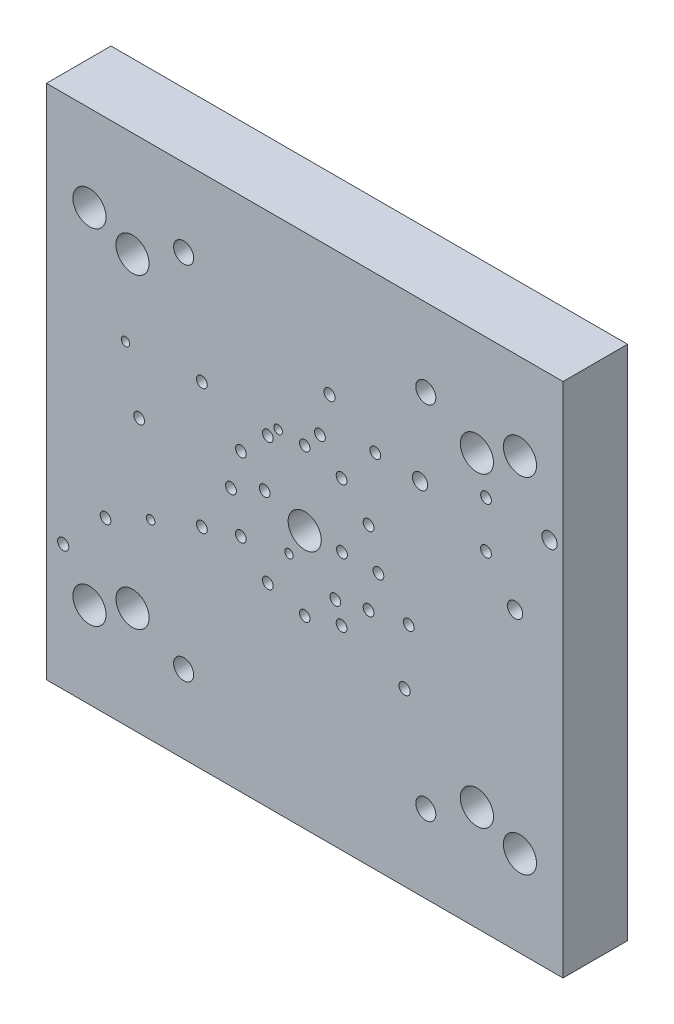
SolidWorks part; units mm, degrees
ref_plane "Front Plane" through (0, 0, 0) normal (0, 0, 1) x (1, 0, 0)
ref_plane "Top Plane" through (0, 0, 0) normal (0, 1, 0) x (1, 0, 0)
ref_plane "Right Plane" through (0, 0, 0) normal (1, 0, 0) x (0, 0, -1)
sketch "Sketch1" plane through (0, 0, 0) normal (0, 0, 1) x (1, 0, 0)
  line L1 (-152.4, 152.4) -> (152.4, 152.4)
  line L2 (-152.4, 152.4) -> (-152.4, -152.4)
  line L3 (-152.4, -152.4) -> (152.4, -152.4)
  line L4 (152.4, 152.4) -> (152.4, -152.4)
  line L5 (-152.4, 152.4) -> (152.4, -152.4) construction
  line L6 (-152.4, -152.4) -> (152.4, 152.4) construction
  point P0 (0, 0)
  dimension "D1" = 304.8
  dimension "D2" = 304.8
extrude "Boss-Extrude1" add sketch "Sketch1" along normal blind 38.1
sketch "Sketch2" plane through (0, 0, 38.1) normal (0, 0, 1) x (1, 0, 0)
  line L0 (-152.4, 0) -> (152.4, 0) construction
  line L5 (-152.4, 152.4) -> (-152.4, -152.4) construction
  line L6 (152.4, -152.4) -> (152.4, 152.4) construction
  line L7 (-152.4, -101.6) -> (152.4, -101.6) construction
  line L8 (-152.4, 101.6) -> (152.4, 101.6) construction
  line L9 (0, 101.6) -> (0, -101.6) construction
  line L10 (127, 101.6) -> (127, -101.6) construction
  line L11 (-127, 101.6) -> (-127, -101.6) construction
  circle A0 centre (-127, 101.6) radius 6.5151
  circle A1 centre (127, 101.6) radius 6.5151
  circle A2 centre (127, -101.6) radius 6.5151
  circle A3 centre (-127, -101.6) radius 6.5151
  circle A4 centre (0, 0) radius 6.5151
  dimension "D5" = 13.0302
  dimension "D1" = 101.6
  dimension "D2" = 101.6
  dimension "D3" = 127
  dimension "D4" = 127
extrude "HAAS T-Slot Holes" cut sketch "Sketch2" against normal through all
sketch "Sketch3" plane through (0, 0, 38.1) normal (0, 0, 1) x (1, 0, 0)
  circle A0 centre (-127, 101.6) radius 9.779
  circle A1 centre (127, 101.6) radius 9.779
  circle A2 centre (0, 0) radius 9.779
  circle A3 centre (127, -101.6) radius 9.779
  circle A4 centre (-127, -101.6) radius 9.779
  dimension "D1" = 19.558
extrude "HAAS Counter Bores" cut sketch "Sketch3" against normal offset from surface (22.225 mm away) 15.875 contours A0 | A1 | A2 | A3 | A4 up to face at (6.5151, 0, 0)
sketch "Sketch4" plane through (0, 0, 38.1) normal (0, 0, 1) x (1, 0, 0)
  line L0 (-127, 90.4875) -> (127, 90.4875) construction
  line L1 (-127, 30.1625) -> (127, 30.1625) construction
  line L2 (-127, 30.1625) -> (-127, -30.1625) construction
  line L3 (-127, -30.1625) -> (127, -30.1625) construction
  line L4 (127, 30.1625) -> (127, -30.1625) construction
  line L5 (-127, 30.1625) -> (127, -30.1625) construction
  line L6 (-127, -30.1625) -> (127, 30.1625) construction
  line L7 (-127, -90.4875) -> (127, -90.4875) construction
  line L8 (-101.6, 90.4875) -> (-101.6, 84.1375) construction
  line L9 (-101.6, -90.4875) -> (-101.6, -84.1375) construction
  line L10 (101.6, -90.4875) -> (101.6, -84.1375) construction
  line L11 (101.6, 90.4875) -> (101.6, 84.1375) construction
  circle A0 centre (-101.6, 90.4875) radius 6.5151
  circle A1 centre (101.6, 90.4875) radius 6.5151
  circle A2 centre (-101.6, -90.4875) radius 6.5151
  circle A3 centre (101.6, -90.4875) radius 6.5151
  point P0 (0, 0)
  dimension "D9" = 13.0302
  dimension "D1" = 60.325
  dimension "D2" = 254
  dimension "D5" = 203.2
  dimension "D6" = 25.4
  dimension "D7" = 203.2
  dimension "D8" = 6.35
  dimension "D3" = 60.325
  dimension "D4" = 60.325
extrude "Tormach T-Slot Holes" cut sketch "Sketch4" against normal through all
sketch "Sketch5" plane through (0, 0, 38.1) normal (0, 0, 1) x (1, 0, 0)
  circle A0 centre (-101.6, 90.4875) radius 9.779
  circle A1 centre (101.6, 90.4875) radius 9.779
  circle A2 centre (101.6, -90.4875) radius 9.779
  circle A3 centre (-101.6, -90.4875) radius 9.779
  dimension "D1" = 19.558
extrude "Tormach Counter bores" cut sketch "Sketch5" against normal up to surface (22.225 mm away) up to face at (-117.221, 101.6, 15.875)
sketch "Sketch6" plane through (0, 0, 38.1) normal (0, 0, 1) x (1, 0, 0)
  circle A0 centre (0, 0) radius 43.5 construction
  circle A1 centre (0, 43.5) radius 3.0734
  circle A2 centre (0, -43.5) radius 3.0734
  dimension "D1" = 87.0001
  dimension "D2" = 6.1468
extrude "Sprocket Locating Holes" cut sketch "Sketch6" against normal blind 6.35
sketch "Sketch7" plane through (0, 0, 38.1) normal (0, 0, 1) x (1, 0, 0)
  circle A0 centre (0, 0) radius 43.5 construction
  circle A2 centre (43.5, 0) radius 3.175
  circle A4 centre (37.6721, -21.75) radius 3.175
  circle A5 centre (21.75, -37.6721) radius 3.175
  circle A6 centre (0, -43.5) radius 3.175 [skipped]
  circle A7 centre (-21.75, -37.6721) radius 3.175
  circle A8 centre (-37.6721, -21.75) radius 3.175
  circle A9 centre (-43.5, 0) radius 3.175
  circle A10 centre (-37.6721, 21.75) radius 3.175
  circle A11 centre (-21.75, 37.6721) radius 3.175
  circle A12 centre (0, 43.5) radius 3.175 [skipped]
  circle A13 centre (21.75, 37.6721) radius 3.175
  circle A14 centre (37.6721, 21.75) radius 3.175
  point P31 (0, 0)
  dimension "D1" = 87.0001
  dimension "D2" = 6.35
  dimension "D3" = 12
extrude "Sprocket Mounting clearance holes" cut sketch "Sketch7" against normal blind 9.525
sketch "Sketch8" plane through (0, 0, 38.1) normal (0, 0, 1) x (1, 0, 0)
  line L1 (-71.4375, 106.4641) -> (71.4375, 106.4641) construction
  line L2 (-71.4375, 106.4641) -> (-71.4375, -106.4641) construction
  line L3 (-71.4375, -106.4641) -> (71.4375, -106.4641) construction
  line L4 (71.4375, 106.4641) -> (71.4375, -106.4641) construction
  line L5 (-71.4375, 106.4641) -> (71.4375, -106.4641) construction
  line L6 (-71.4375, -106.4641) -> (71.4375, 106.4641) construction
  circle A0 centre (-71.4375, 106.4641) radius 5.9182
  circle A1 centre (71.4375, 106.4641) radius 5.9182
  circle A2 centre (71.4375, -106.4641) radius 5.9182
  circle A3 centre (-71.4375, -106.4641) radius 5.9182
  point P0 (0, 0)
  dimension "D3" = 11.8364
  dimension "D1" = 142.875
  dimension "D2" = 212.9282
extrude "1/2-13 Tapped Holes" cut sketch "Sketch8" against normal blind 19.05
sketch "Sketch9" plane through (0, 0, 38.1) normal (0, 0, 1) x (1, 0, 0)
  circle A0 centre (-117.5189, -52.2876) radius 3.175
  circle A1 centre (-60.6634, -28.4101) radius 3.175
  circle A2 centre (-60.6634, 45.677) radius 3.175
  circle A3 centre (-23.6198, 8.6335) radius 3.175
  circle A4 centre (-97.707, 8.6335) radius 3.175
  circle A5 centre (18.0623, -26.1797) radius 3.175
  circle A6 centre (21.9762, 0) radius 3.175
  circle A7 centre (61.3833, -17.3739) radius 3.175
  circle A8 centre (106.976, 70.3959) radius 3.175
  circle A9 centre (106.976, 42.9004) radius 3.175
  circle A10 centre (144.4539, 67.4373) radius 4.5
  circle A11 centre (124.1092, 21.6131) radius 4.5
  circle A12 centre (68.0681, 59.3279) radius 4.5
  circle A13 centre (58.9353, -51.2652) radius 3.3
  circle A14 centre (-142.4923, -78.095) radius 3.3
  circle A15 centre (-105.7351, 43.7713) radius 2.5
  circle A16 centre (-90.8975, -39.8642) radius 2.5
  circle A17 centre (-9.2711, -16.3656) radius 2.5
  circle A18 centre (-15.6655, 43.8657) radius 2.5
  circle A20 centre (14.6267, 76.8405) radius 3.3
  circle A21 centre (8.9855, 53.4682) radius 3.175
  circle A22 centre (41.6559, 60.6579) radius 3.175
extrude "Cut-Extrude1" cut sketch "Sketch9" against normal blind 19.05
ref_axis "Axis1" through (0, 0, 0) along (0, 0, 1)
